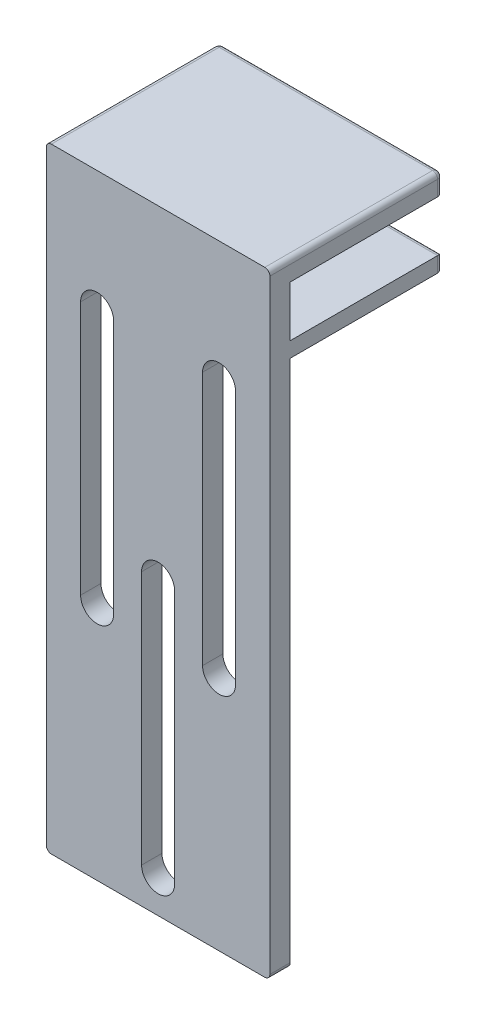
SolidWorks part; units mm, degrees
ref_plane "前视基准面" through (0, 0, 0) normal (0, 0, 1) x (1, 0, 0)
ref_plane "上视基准面" through (0, 0, 0) normal (0, 1, 0) x (1, 0, 0)
ref_plane "右视基准面" through (0, 0, 0) normal (1, 0, 0) x (0, 0, -1)
other "Configuration Table"
sketch "草图1" plane through (0, 0, 0) normal (0, 0, 1) x (1, 0, 0)
  line L0 (-21, 0) -> (21, 0)
  line L1 (22, 1) -> (22, 120)
  line L2 (21, 121) -> (-21, 121)
  line L3 (-22, 120) -> (-22, 1)
  line L4 (0, 7) -> (0, 57) construction
  line L5 (-3.25, 7) -> (-3.25, 57)
  line L6 (3.25, 7) -> (3.25, 57)
  line L7 (0, 0) -> (0, 42.4714) construction
  line L8 (-12, 97) -> (-12, 47) construction
  line L9 (-8.75, 97) -> (-8.75, 47)
  line L10 (-15.25, 97) -> (-15.25, 47)
  line L11 (-22, 117) -> (22, 117)
  line L12 (-22, 107) -> (22, 107)
  line L13 (-22, 104) -> (22, 104)
  line L14 (12, 97) -> (12, 47) construction
  line L15 (8.75, 97) -> (8.75, 47)
  line L16 (15.25, 97) -> (15.25, 47)
  arc A0 (-3.25, 7) -> (3.25, 7) centre (0, 7) ccw
  arc A1 (3.25, 57) -> (-3.25, 57) centre (0, 57) ccw
  arc A2 (-8.75, 97) -> (-15.25, 97) centre (-12, 97) ccw
  arc A3 (-15.25, 47) -> (-8.75, 47) centre (-12, 47) ccw
  arc A4 (8.75, 97) -> (15.25, 97) centre (12, 97) cw
  arc A5 (15.25, 47) -> (8.75, 47) centre (12, 47) cw
  arc A6 (-22, 1) -> (-21, 0) centre (-21, 1) ccw
  arc A7 (22, 1) -> (21, 0) centre (21, 1) cw
  arc A8 (22, 120) -> (21, 121) centre (21, 120) ccw
  arc A9 (-21, 121) -> (-22, 120) centre (-21, 120) ccw
  point P7 (0, 32)
  point P16 (-12, 72)
  point P29 (12, 72)
  point P36 (-22, 0)
  point P39 (22, 0)
  point P44 (-22, 121)
  dimension "D13" = 1
  dimension "D1" = 44
  dimension "D2" = 6.5
  dimension "D3" = 121
  dimension "D4" = 7
  dimension "D5" = 12
  dimension "D6" = 6.5
  dimension "D7" = 40
  dimension "D8" = 50
  dimension "D9" = 40
  dimension "D10" = 4
  dimension "D11" = 10
  dimension "D12" = 3
extrude "凸台-拉伸1" add sketch "草图1" along normal blind 4 contours A7 L1 L13 L3 A6 L0 A3 L10 A2 L9 A1 L6 A0 L5 L16 A5 L15 A4 | L3 L13 L1 L12 | L3 L12 L1 L11 | L2 A9 L3 L11 L1 A8 region at (-20.9086, 1.0914, 0) region at (0, 105.5, 0) region at (0, 112, 0) region at (0, 118.9957, 0)
extrude "凸台-拉伸2" add sketch "草图1<3>" against normal blind 30 contours L3 L13 L1 L12 | L2 A9 L3 L11 L1 A8 region at (0, 105.5, 0) region at (0, 118.9957, 0)
sketch "草图1<3>" plane through (0, 0, 0) normal (0, 0, 1) x (1, 0, 0) same geometry as "草图1"
fillet "圆角1" radius 1 10 edges at (-22, 118.5, -30) (-21.7071, 120.7071, -30) (0, 121, -30) (21.7071, 120.7071, -30) (0, 104, -30) (0, 107, -30) (0, 117, -30) (22, 118.5, -30) (-22, 105.5, -30) (22, 105.5, -30)
